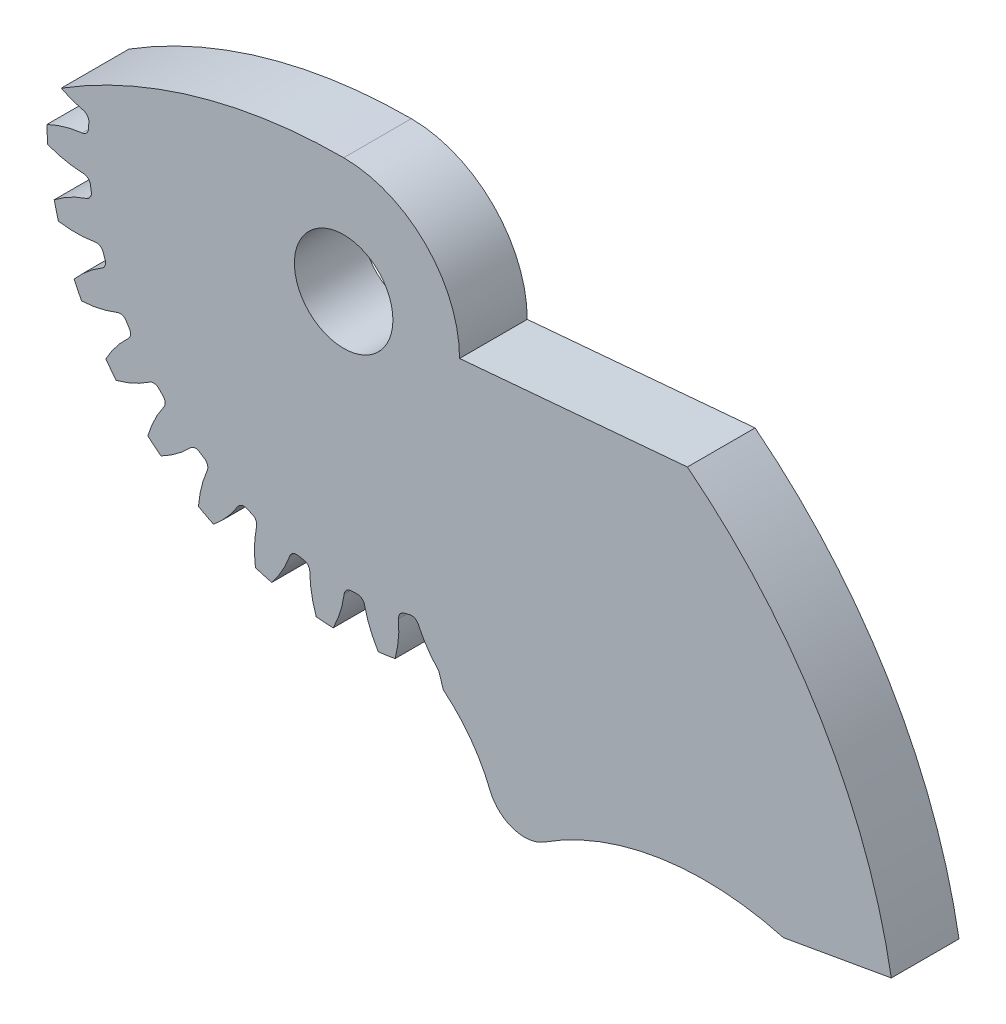
SolidWorks part; units mm, degrees
material "Delrin 2700 NC010, Low Viscosity Acetal Copolymer (SS)"
ref_plane "Front" through (0, 0, 0) normal (0, 0, 1) x (1, 0, 0)
ref_plane "Top" through (0, 0, 0) normal (0, 1, 0) x (1, 0, 0)
ref_plane "Right" through (0, 0, 0) normal (1, 0, 0) x (0, 0, -1)
sketch "Sketch3" plane through (0, 0, 0) normal (0, 0, 1) x (1, 0, 0)
  circle A0 centre (0, 0) radius 40.64
  dimension "od" = 81.28
extrude "gearBody" add sketch "Sketch3" along normal blind 25.4
sketch "Sketch2" plane through (0, 0, 0) normal (0, 0, 1) x (1, 0, 0)
  line L0 (0, 0) -> (34.0786, 14.1158) construction
  line L1 (45.4751, -11.4855) -> (0, 0) construction
  line L2 (0, 0) -> (36.3143, 0) construction
  line L3 (38.0972, -0.458) -> (37.8451, -4.4001) construction
  line L5 (37.9712, -2.4291) -> (0, 0) construction
  line L7 (0, 0) -> (36.8864, 0) construction
  arc A0 (36.879, -0.7403) -> (36.6727, -3.9649) centre (0, 0) ccw construction
  arc A1 (40.637, 0.4947) -> (40.2427, -5.6687) centre (0, 0) ccw construction
  arc A2 (38.0972, -0.458) -> (37.8451, -4.4001) centre (0, 0) ccw construction
  arc A3 (34.9015, -2.6404) -> (34.9534, -1.8283) centre (0, 0) ccw
  arc A4 (45.4751, -11.4855) -> (35.6466, -3.6712) centre (32.0022, -18.3431) ccw
  arc A5 (45.4751, -11.4855) -> (46.5679, 5.5974) centre (0, 0) ccw
  arc A6 (46.5679, 5.5974) -> (35.8238, -0.9008) centre (34.0786, 14.1158) cw
  arc A7 (34.9534, -1.8283) -> (35.8238, -0.9008) centre (35.9376, -1.8798) cw
  arc A8 (35.6466, -3.6712) -> (34.9015, -2.6404) centre (35.8842, -2.7147) cw
  point P6 (46.5679, 5.5974)
  point P22 (45.4751, -11.4855)
  dimension "baseDia" = 73.7729
  dimension "od" = 81.28
  dimension "pd" = 76.2
  dimension "rd" = 70.0024
  dimension "rFillet" = 0.9855
  dimension "pointX" = 46.5679
  dimension "pointY" = 5.5974
  dimension "CTT" = 3.9421
  dimension "flankCenterAngle" = 22.5
extrude "toothCut" cut sketch "Sketch2" along normal through all
pattern_circular "CirPattern1" count 30 over 360 about axis through (0, 0, 25.4) along (0, 0, -1) of "toothCut"
sketch "hub1Dia" plane through (0, 0, 0) normal (0, 0, -1) x (-1, 0, 0)
  circle A0 centre (0, 0) radius 12.7
  dimension "hub1Dia" = 25.4
sketch "hub2Dia" plane through (0, 0, 25.4) normal (0, 0, 1) x (1, 0, 0)
  circle A0 centre (0, 0) radius 12.7
  dimension "hub2dia" = 25.4
sketch "boreDia" plane through (0, 0, 0) normal (0, 0, 1) x (1, 0, 0)
  circle A0 centre (0, 0) radius 9.525
  dimension "boreDia" = 19.05
extrude "bore" cut sketch "boreDia" against normal mid plane 25400
sketch "Sketch4" plane through (0, 0, 25.4) normal (0, 0, 1) x (1, 0, 0)
  circle A0 centre (0, -57.15) radius 76.1746
  arc A2 (-41.7195, 6.5842) -> (41.7195, 6.5842) centre (0, 0) cw
  dimension "D1" = 152.3492
  dimension "D2" = 57.15
extrude "Cut-Extrude1" cut sketch "Sketch4" against normal through all contours A0 region at (0, 26.0638, 25.4)
sketch "Sketch5" plane through (0, 0, 25.4) normal (0, 0, 1) x (1, 0, 0)
  line L0 (0, 19.0246) -> (21.5163, 0.2011)
  line L1 (21.5163, 0.2011) -> (8.9608, -26.928)
  line L2 (8.9608, -26.928) -> (13.028, -38.4952)
  line L3 (0, 0) -> (0, -57.15) construction
  line L4 (0, -57.15) -> (-48.0548, 1.9542) construction
  line L5 (0, -57.15) -> (65.9691, -95.2373) construction
  line L6 (13.6543, -40.4261) -> (13.028, -38.4952)
  line L9 (0, -57.15) -> (75.0173, -43.9224) construction
  line L12 (60.232, -46.5295) -> (75.0173, -43.9224)
  circle A1 centre (0, -57.15) radius 76.1746 construction
  arc A4 (33.1977, 11.4101) -> (-34.0662, 10.9827) centre (0, -57.15) ccw construction
  arc A5 (0, 19.0246) -> (75.0173, -43.9224) centre (0, -57.15) cw
  circle A6 centre (0, -57.15) radius 21.59 construction
  arc A9 (33.1977, 11.4101) -> (-34.0662, 10.9827) centre (0, -57.15) ccw construction
  arc A10 (20.0525, -49.1485) -> (13.6543, -40.4261) centre (0, -57.15) ccw
  circle A12 centre (49.4934, -85.725) radius 40.64 construction
  arc A13 (27.5177, -51.539) -> (60.232, -46.5295) centre (49.4934, -85.725) cw
  arc A14 (27.5177, -51.539) -> (20.0525, -49.1485) centre (24.7708, -47.2658) cw
  point P28 (21.569, -56.1981)
  dimension "D1" = 43.18
  dimension "D3" = 81.28
  dimension "D7" = 5.08
  dimension "D2" = 120
  dimension "D4" = 57.15
  dimension "D5" = 80
extrude "Boss-Extrude1" add sketch "Sketch5" against normal up to surface (25.4 mm away) up to face at (9.525, 0, 0)
sketch "Sketch6" plane through (0, 0, 0) normal (0, 1, 0) x (1, 0, 0)
  line L0 (-46.1384, -9.271) -> (97.8162, -9.271)
  line L4 (97.8162, -9.271) -> (71.9328, -41.1538)
  line L5 (71.9328, -41.1538) -> (-48.6783, -38.0647)
  line L6 (-48.6783, -38.0647) -> (-46.1384, -9.271)
  dimension "D1" = 9.271
extrude "Cut-Extrude2" cut sketch "Sketch6" against normal through all both and the other way through all
sketch "Sketch7" plane through (0, 0, 9.271) normal (0, 0, 1) x (1, 0, 0)
  line L8 (15.875, 0) -> (50.2154, 3.0044)
  line L9 (-43.0106, 8.3498) -> (-40.0828, 3.8911)
  line L10 (0, -57.15) -> (-43.0106, 8.3498) construction
  line L11 (0, 0) -> (80.4469, 0) construction
  arc A0 (-40.2427, 5.6687) -> (-35.6466, 3.6712) centre (-32.0022, 18.3431) ccw construction
  circle A3 centre (0, -57.15) radius 73.025 construction
  circle A4 centre (0, 0) radius 15.875 construction
  arc A5 (0, 15.875) -> (15.875, 0) centre (0, 0) cw
  circle A8 centre (0, -57.15) radius 78.359 construction
  arc A9 (-43.0106, 8.3498) -> (50.2154, 3.0044) centre (0, -57.15) cw
  arc A10 (0, 15.875) -> (-40.0828, 3.8911) centre (0, -57.15) ccw
  point P0 (-36.4485, 3.894)
  dimension "D2" = 57.15
  dimension "D1" = 146.05
  dimension "D3" = 156.718
  dimension "D4" = 5
extrude "Cut-Extrude3" cut sketch "Sketch7" against normal through all both
sketch "Sketch8" plane through (0, 0, 9.271) normal (0, 0, 1) x (1, 0, 0)
  circle A0 centre (0, 0) radius 6.7469
  circle A1 centre (0, 0) radius 10.9012
  dimension "D1" = 13.4937
extrude "Boss-Extrude2" add sketch "Sketch8" against normal up to surface (9.271 mm away) up to face at (9.525, 0, 0)
equation "\"Bodytube_OD\" = 6.17in"
equation "\"Bodytube_ID\" = 5.998in"
equation "\"Fwd_Tube_Length\" = 38in"
equation "\"Mid_Tube_Length\" = 8in"
equation "\"Aft_Section_Length\"= 40in"
equation "\"Mid_Coupler_Length\" = 13in"
equation "\"Aft_Lower_Length\"= 22in"
equation "\"AB_Coupler_OD_Length\"= 1in"
equation "\"AB_Coupling_Section_Length\"= 0.375in"
equation "\"AB_Coupler_Length\"= \"AB_Coupler_OD_Length\" + \"AB_Coupling_Section_Length\" * 2"
equation "\"Cutout_Angle\" = 80"
equation "\"AB_Paddle_Height\" = 0.375in"
equation "\"AB_Coupler_Num_Screws\"= 6"
equation "\"Num_Cutouts\" = 3"
equation "\"AB_Coupler_OD\"= 6.17in"
equation "\"AB_Coupler_ID\"= 5.75in"
equation "\"AB_Coupler_Surface_Diameter\"= 5.998in"
equation "\"AB_Coupling_Screw_Diameter\"= 0.1065in"
equation "\"AB_Central_Bushing_Length\" = .75in"
equation "\"Lead_Screw_Dist\" = 2.25in"
equation "\"Lead_Screw_Diam\" = (27/64)*1in"
equation "\"Lead_Screw_Length\" = (\"Mid_Coupler_Length\" + 2*0.375in + 2*0.5in)"
equation "\"Paddle_Pin_Offset\" = .25in"
equation "\"Paddle_Pin_Radius\" = 2.25in"
equation "\"Fwd_BKHD_From_Top\" = 18in"
equation "\"D1@Sketch4\"=\"Bodytube_ID\""
equation "\"D2@Sketch4\"=\"Paddle_Pin_Radius\""
equation "\"D3@Sketch5\"=\"Paddle_Gear_OD\""
equation "\"D4@Sketch5\"=\"Paddle_Pin_Radius\""
equation "\"Motor_OD\" = 4in"
equation "\"Aft_Upper_Length\"= \"Aft_Section_Length\" - \"Aft_Lower_Length\" - \"AB_Coupler_OD_Length\""
equation "\"Paddle_Gear_OD\" = 3.2in"
equation "\"D5@Sketch5\"=\"Cutout_Angle\""
equation "\"D1@Sketch7\"=\"AB_Coupler_ID\""
equation "\"D2@Sketch7\"=\"Paddle_Pin_Radius\""
equation "\"D3@Sketch7\"=\"Bodytube_OD\""
